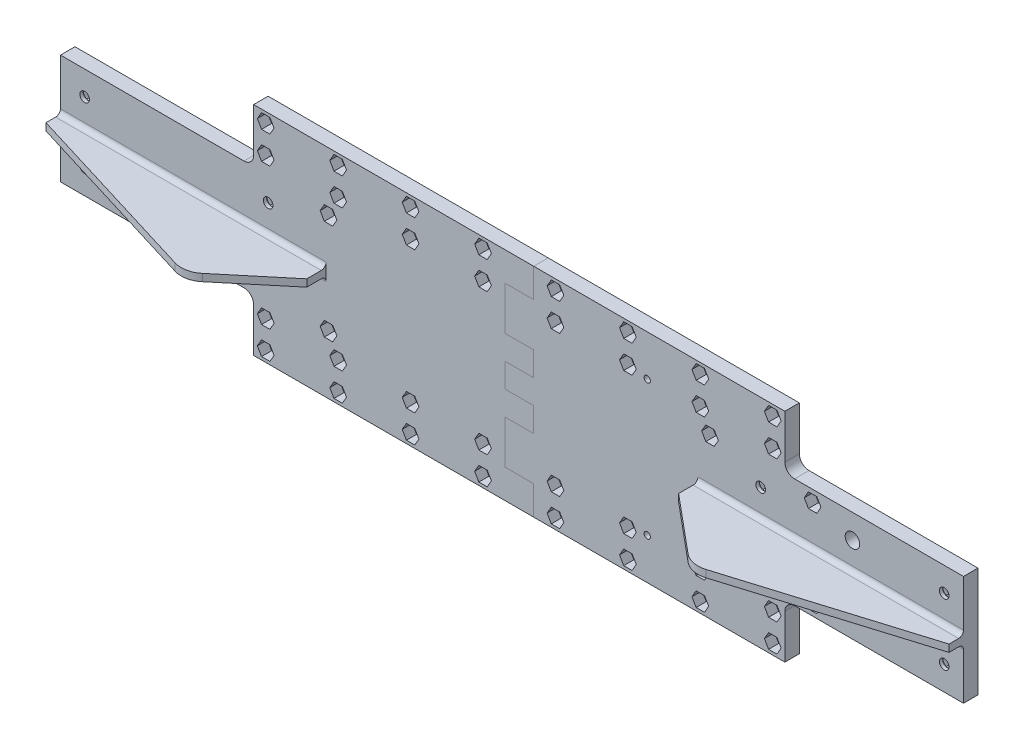
SolidWorks part; units mm, degrees
ref_plane "Top Plane" through (0, 0, 0) normal (0, 0, 1) x (1, 0, 0)
ref_plane "Right Plane" through (0, 0, 0) normal (0, 1, 0) x (1, 0, 0)
ref_plane "Front Plane" through (0, 0, 0) normal (1, 0, 0) x (0, 0, -1)
sketch "Sketch1" plane through (0, 0, 0) normal (0, 0, 1) x (1, 0, 0)
  line L0 (-187, 81) -> (187, -81) construction
  line L1 (-187, 81) -> (187, 81) construction
  line L2 (-187, 81) -> (-187, -81) construction
  line L3 (-187, -81) -> (187, -81) construction
  line L4 (187, 81) -> (187, -81) construction
  line L5 (-187, -22.75) -> (-107, -22.75) construction
  line L6 (-107, -22.75) -> (-107, -81) construction
  line L7 (113, -81) -> (113, -22.75) construction
  line L8 (113, -22.75) -> (187, -22.75) construction
  line L9 (-187, 0) -> (187, 0) construction
  line L10 (113, 22.75) -> (187, 22.75) construction
  line L11 (113, 81) -> (113, 22.75) construction
  line L12 (-107, 22.75) -> (-107, 81) construction
  line L13 (-187, 22.75) -> (-107, 22.75) construction
  line L14 (85.2, -81) -> (85.2, 81) construction
  line L15 (-93, -81) -> (-93, 81) construction
  line L16 (-187, -2.75) -> (187, -2.75) construction
  line L17 (187, 2.75) -> (-187, 2.75) construction
  text T0 "FRONT" font "Century Gothic" height in points 80
  dimension "D1" = 374
  dimension "D2" = 162
  dimension "D3" = 45.5
  dimension "D4" = 80
  dimension "D5" = 74
  dimension "D6" = 27.8
  dimension "D7" = 14
  dimension "D8" = 20
  dimension "D9" = 20
sketch "Sketch2" plane through (0, 0, 0) normal (0, 0, 1) x (1, 0, 0)
  line L0 (-187, 81) -> (-187, -81) construction
  line L1 (-187, 81) -> (187, 81) construction
  line L2 (187, 81) -> (187, -81) construction
  line L3 (-187, -81) -> (187, -81) construction
  line L4 (113, -81) -> (113, -22.75) construction
  line L5 (113, -22.75) -> (187, -22.75) construction
  line L6 (113, 22.75) -> (187, 22.75) construction
  line L7 (113, 81) -> (113, 22.75) construction
  line L8 (-107, 22.75) -> (-107, 81) construction
  line L9 (-187, 22.75) -> (-107, 22.75) construction
  line L10 (-107, -22.75) -> (-107, -81) construction
  line L11 (-187, -22.75) -> (-107, -22.75) construction
  line L12 (-187, 22.75) -> (-187, -22.75)
  line L13 (-107, 81) -> (113, 81)
  line L14 (187, 22.75) -> (187, -22.75)
  line L15 (-107, -81) -> (113, -81)
  line L16 (113, -81) -> (113, -22.75)
  line L17 (113, -22.75) -> (187, -22.75)
  line L18 (113, 22.75) -> (187, 22.75)
  line L19 (113, 81) -> (113, 22.75)
  line L20 (-107, 22.75) -> (-107, 81)
  line L21 (-187, 22.75) -> (-107, 22.75)
  line L22 (-107, -22.75) -> (-107, -81)
  line L23 (-187, -22.75) -> (-107, -22.75)
extrude "Boss-Extrude1" add sketch "Sketch2" along normal mid plane 6
sketch "Sketch5" plane through (0, 0, -3) normal (0, 0, -1) x (-1, 0, 0)
  line L0 (0, 81) -> (0, -81) construction
  line L1 (187, 81) -> (-187, 81) construction
  line L2 (187, -81) -> (-187, -81) construction
  line L4 (-179, 0) -> (177, 0) construction
  line L5 (-179, 12.75) -> (-103, 12.75) construction
  line L6 (-179, 12.75) -> (-179, -12.75) construction
  line L7 (-179, -12.75) -> (-103, -12.75) construction
  line L8 (-103, 12.75) -> (-103, -12.75) construction
  line L9 (101, 12.75) -> (177, 12.75) construction
  line L10 (101, 12.75) -> (101, -12.75) construction
  line L11 (101, -12.75) -> (177, -12.75) construction
  line L12 (177, 12.75) -> (177, -12.75) construction
  circle A8 centre (-103, -12.75) radius 2
  circle A9 centre (-103, 12.75) radius 2
  circle A10 centre (-179, 12.75) radius 2
  circle A11 centre (-179, -12.75) radius 2
  circle A12 centre (177, 12.75) radius 2
  circle A13 centre (177, -12.75) radius 2
  circle A14 centre (101, -12.75) radius 2
  circle A15 centre (101, 12.75) radius 2
  dimension "D3" = 25.5
  dimension "D6" = 4
  dimension "D1" = 76
  dimension "D2" = 103
  dimension "D4" = 101
  dimension "D5" = 76
extrude "Cut-Extrude2" cut sketch "Sketch5" against normal up to next
sketch "Sketch9" plane through (0, 0, 3) normal (0, 0, 1) x (1, 0, 0)
  line L0 (-107.9535, -35) -> (101.269, -35) construction
  line L1 (-12, -40.75) -> (18, -40.75) construction
  line L2 (-12, -29.25) -> (-42, -29.25) construction
  line L3 (-12, -29.25) -> (18, -29.25) construction
  line L4 (-194.5845, 0) -> (205.1662, 0) construction
  line L5 (3, -85.4344) -> (3, 85.4344) construction
  line L6 (-12, -40.75) -> (-42, -40.75) construction
  line L7 (-107, 81) -> (113, -81) construction
  line L8 (-40.2679, -37.75) -> (-43.7321, -37.75) construction
  line L9 (-13.7321, -37.75) -> (-15.4641, -40.75) construction
  line L10 (-15.4641, -40.75) -> (-13.7321, -43.75) construction
  line L11 (-13.7321, -43.75) -> (-10.2679, -43.75) construction
  line L12 (-10.2679, -43.75) -> (-8.5359, -40.75) construction
  line L13 (-8.5359, -40.75) -> (-10.2679, -37.75) construction
  line L14 (-10.2679, -37.75) -> (-13.7321, -37.75) construction
  line L15 (-43.7321, -37.75) -> (-45.4641, -40.75) construction
  line L16 (-45.4641, -40.75) -> (-43.7321, -43.75) construction
  line L17 (-43.7321, -43.75) -> (-40.2679, -43.75) construction
  line L18 (-40.2679, -43.75) -> (-38.5359, -40.75) construction
  line L19 (-38.5359, -40.75) -> (-40.2679, -37.75) construction
  line L20 (-70.2679, -37.75) -> (-73.7321, -37.75) construction
  line L21 (-73.7321, -37.75) -> (-75.4641, -40.75) construction
  line L22 (-75.4641, -40.75) -> (-73.7321, -43.75) construction
  line L23 (-73.7321, -43.75) -> (-70.2679, -43.75) construction
  line L24 (-70.2679, -43.75) -> (-68.5359, -40.75) construction
  line L25 (-68.5359, -40.75) -> (-70.2679, -37.75) construction
  line L26 (-100.2679, -37.75) -> (-103.7321, -37.75) construction
  line L27 (-103.7321, -37.75) -> (-105.4641, -40.75) construction
  line L28 (-105.4641, -40.75) -> (-103.7321, -43.75) construction
  line L29 (-103.7321, -43.75) -> (-100.2679, -43.75) construction
  line L30 (-100.2679, -43.75) -> (-98.5359, -40.75) construction
  line L31 (-98.5359, -40.75) -> (-100.2679, -37.75) construction
  line L32 (-43.7321, -37.75) -> (-40.2679, -43.75) construction
  line L33 (-42, -40.75) -> (-12, -40.75) construction
  line L34 (-8.5359, -29.25) -> (-10.2679, -32.25) construction
  line L35 (-10.2679, -26.25) -> (-8.5359, -29.25) construction
  line L36 (-13.7321, -26.25) -> (-10.2679, -26.25) construction
  line L37 (-15.4641, -29.25) -> (-13.7321, -26.25) construction
  line L38 (-13.7321, -32.25) -> (-15.4641, -29.25) construction
  line L39 (-10.2679, -32.25) -> (-13.7321, -32.25) construction
  line L40 (-43.7321, -26.25) -> (-40.2679, -26.25) construction
  line L41 (-45.4641, -29.25) -> (-43.7321, -26.25) construction
  line L42 (-43.7321, -32.25) -> (-45.4641, -29.25) construction
  line L43 (-40.2679, -32.25) -> (-43.7321, -32.25) construction
  line L44 (-38.5359, -29.25) -> (-40.2679, -32.25) construction
  line L45 (-40.2679, -26.25) -> (-38.5359, -29.25) construction
  line L46 (-73.7321, -26.25) -> (-70.2679, -26.25) construction
  line L47 (-75.4641, -29.25) -> (-73.7321, -26.25) construction
  line L48 (-73.7321, -32.25) -> (-75.4641, -29.25) construction
  line L49 (-70.2679, -32.25) -> (-73.7321, -32.25) construction
  line L50 (-68.5359, -29.25) -> (-70.2679, -32.25) construction
  line L51 (-70.2679, -26.25) -> (-68.5359, -29.25) construction
  line L52 (-103.7321, -26.25) -> (-100.2679, -26.25) construction
  line L53 (-105.4641, -29.25) -> (-103.7321, -26.25) construction
  line L54 (-103.7321, -32.25) -> (-105.4641, -29.25) construction
  line L55 (-100.2679, -32.25) -> (-103.7321, -32.25) construction
  line L56 (-98.5359, -29.25) -> (-100.2679, -32.25) construction
  line L57 (-100.2679, -26.25) -> (-98.5359, -29.25) construction
  line L58 (106.2679, -26.25) -> (104.5359, -29.25) construction
  line L59 (104.5359, -29.25) -> (106.2679, -32.25) construction
  line L60 (106.2679, -32.25) -> (109.7321, -32.25) construction
  line L61 (109.7321, -32.25) -> (111.4641, -29.25) construction
  line L62 (111.4641, -29.25) -> (109.7321, -26.25) construction
  line L63 (109.7321, -26.25) -> (106.2679, -26.25) construction
  line L64 (76.2679, -26.25) -> (74.5359, -29.25) construction
  line L65 (74.5359, -29.25) -> (76.2679, -32.25) construction
  line L66 (76.2679, -32.25) -> (79.7321, -32.25) construction
  line L67 (79.7321, -32.25) -> (81.4641, -29.25) construction
  line L68 (81.4641, -29.25) -> (79.7321, -26.25) construction
  line L69 (79.7321, -26.25) -> (76.2679, -26.25) construction
  line L70 (46.2679, -26.25) -> (44.5359, -29.25) construction
  line L71 (44.5359, -29.25) -> (46.2679, -32.25) construction
  line L72 (46.2679, -32.25) -> (49.7321, -32.25) construction
  line L73 (49.7321, -32.25) -> (51.4641, -29.25) construction
  line L74 (51.4641, -29.25) -> (49.7321, -26.25) construction
  line L75 (49.7321, -26.25) -> (46.2679, -26.25) construction
  line L76 (16.2679, -32.25) -> (19.7321, -32.25) construction
  line L77 (19.7321, -32.25) -> (21.4641, -29.25) construction
  line L78 (21.4641, -29.25) -> (19.7321, -26.25) construction
  line L79 (19.7321, -26.25) -> (16.2679, -26.25) construction
  line L80 (16.2679, -26.25) -> (14.5359, -29.25) construction
  line L81 (14.5359, -29.25) -> (16.2679, -32.25) construction
  line L82 (48, -40.75) -> (18, -40.75) construction
  line L83 (49.7321, -37.75) -> (46.2679, -43.75) construction
  line L84 (104.5359, -40.75) -> (106.2679, -37.75) construction
  line L85 (106.2679, -43.75) -> (104.5359, -40.75) construction
  line L86 (109.7321, -43.75) -> (106.2679, -43.75) construction
  line L87 (111.4641, -40.75) -> (109.7321, -43.75) construction
  line L88 (109.7321, -37.75) -> (111.4641, -40.75) construction
  line L89 (106.2679, -37.75) -> (109.7321, -37.75) construction
  line L90 (74.5359, -40.75) -> (76.2679, -37.75) construction
  line L91 (76.2679, -43.75) -> (74.5359, -40.75) construction
  line L92 (79.7321, -43.75) -> (76.2679, -43.75) construction
  line L93 (81.4641, -40.75) -> (79.7321, -43.75) construction
  line L94 (79.7321, -37.75) -> (81.4641, -40.75) construction
  line L95 (76.2679, -37.75) -> (79.7321, -37.75) construction
  line L96 (44.5359, -40.75) -> (46.2679, -37.75) construction
  line L97 (46.2679, -43.75) -> (44.5359, -40.75) construction
  line L98 (49.7321, -43.75) -> (46.2679, -43.75) construction
  line L99 (51.4641, -40.75) -> (49.7321, -43.75) construction
  line L100 (49.7321, -37.75) -> (51.4641, -40.75) construction
  line L101 (16.2679, -37.75) -> (19.7321, -37.75) construction
  line L102 (14.5359, -40.75) -> (16.2679, -37.75) construction
  line L103 (16.2679, -43.75) -> (14.5359, -40.75) construction
  line L104 (19.7321, -43.75) -> (16.2679, -43.75) construction
  line L105 (21.4641, -40.75) -> (19.7321, -43.75) construction
  line L106 (19.7321, -37.75) -> (21.4641, -40.75) construction
  line L107 (46.2679, -37.75) -> (49.7321, -37.75) construction
  line L108 (46.2679, 37.75) -> (49.7321, 37.75) construction
  line L109 (19.7321, 37.75) -> (21.4641, 40.75) construction
  line L110 (21.4641, 40.75) -> (19.7321, 43.75) construction
  line L111 (19.7321, 43.75) -> (16.2679, 43.75) construction
  line L112 (16.2679, 43.75) -> (14.5359, 40.75) construction
  line L113 (14.5359, 40.75) -> (16.2679, 37.75) construction
  line L114 (16.2679, 37.75) -> (19.7321, 37.75) construction
  line L115 (49.7321, 37.75) -> (51.4641, 40.75) construction
  line L116 (51.4641, 40.75) -> (49.7321, 43.75) construction
  line L117 (49.7321, 43.75) -> (46.2679, 43.75) construction
  line L118 (46.2679, 43.75) -> (44.5359, 40.75) construction
  line L119 (44.5359, 40.75) -> (46.2679, 37.75) construction
  line L120 (76.2679, 37.75) -> (79.7321, 37.75) construction
  line L121 (79.7321, 37.75) -> (81.4641, 40.75) construction
  line L122 (81.4641, 40.75) -> (79.7321, 43.75) construction
  line L123 (79.7321, 43.75) -> (76.2679, 43.75) construction
  line L124 (76.2679, 43.75) -> (74.5359, 40.75) construction
  line L125 (74.5359, 40.75) -> (76.2679, 37.75) construction
  line L126 (106.2679, 37.75) -> (109.7321, 37.75) construction
  line L127 (109.7321, 37.75) -> (111.4641, 40.75) construction
  line L128 (111.4641, 40.75) -> (109.7321, 43.75) construction
  line L129 (109.7321, 43.75) -> (106.2679, 43.75) construction
  line L130 (106.2679, 43.75) -> (104.5359, 40.75) construction
  line L131 (104.5359, 40.75) -> (106.2679, 37.75) construction
  line L132 (49.7321, 37.75) -> (46.2679, 43.75) construction
  line L133 (48, 40.75) -> (18, 40.75) construction
  line L134 (14.5359, 29.25) -> (16.2679, 32.25) construction
  line L135 (16.2679, 26.25) -> (14.5359, 29.25) construction
  line L136 (19.7321, 26.25) -> (16.2679, 26.25) construction
  line L137 (21.4641, 29.25) -> (19.7321, 26.25) construction
  line L138 (19.7321, 32.25) -> (21.4641, 29.25) construction
  line L139 (16.2679, 32.25) -> (19.7321, 32.25) construction
  line L140 (49.7321, 26.25) -> (46.2679, 26.25) construction
  line L141 (51.4641, 29.25) -> (49.7321, 26.25) construction
  line L142 (49.7321, 32.25) -> (51.4641, 29.25) construction
  line L143 (46.2679, 32.25) -> (49.7321, 32.25) construction
  line L144 (44.5359, 29.25) -> (46.2679, 32.25) construction
  line L145 (46.2679, 26.25) -> (44.5359, 29.25) construction
  line L146 (79.7321, 26.25) -> (76.2679, 26.25) construction
  line L147 (81.4641, 29.25) -> (79.7321, 26.25) construction
  line L148 (79.7321, 32.25) -> (81.4641, 29.25) construction
  line L149 (76.2679, 32.25) -> (79.7321, 32.25) construction
  line L150 (74.5359, 29.25) -> (76.2679, 32.25) construction
  line L151 (76.2679, 26.25) -> (74.5359, 29.25) construction
  line L152 (109.7321, 26.25) -> (106.2679, 26.25) construction
  line L153 (111.4641, 29.25) -> (109.7321, 26.25) construction
  line L154 (109.7321, 32.25) -> (111.4641, 29.25) construction
  line L155 (106.2679, 32.25) -> (109.7321, 32.25) construction
  line L156 (104.5359, 29.25) -> (106.2679, 32.25) construction
  line L157 (106.2679, 26.25) -> (104.5359, 29.25) construction
  line L158 (-100.2679, 26.25) -> (-98.5359, 29.25) construction
  line L159 (-98.5359, 29.25) -> (-100.2679, 32.25) construction
  line L160 (-100.2679, 32.25) -> (-103.7321, 32.25) construction
  line L161 (-103.7321, 32.25) -> (-105.4641, 29.25) construction
  line L162 (-105.4641, 29.25) -> (-103.7321, 26.25) construction
  line L163 (-103.7321, 26.25) -> (-100.2679, 26.25) construction
  line L164 (-70.2679, 26.25) -> (-68.5359, 29.25) construction
  line L165 (-68.5359, 29.25) -> (-70.2679, 32.25) construction
  line L166 (-70.2679, 32.25) -> (-73.7321, 32.25) construction
  line L167 (-73.7321, 32.25) -> (-75.4641, 29.25) construction
  line L168 (-75.4641, 29.25) -> (-73.7321, 26.25) construction
  line L169 (-73.7321, 26.25) -> (-70.2679, 26.25) construction
  line L170 (-40.2679, 26.25) -> (-38.5359, 29.25) construction
  line L171 (-38.5359, 29.25) -> (-40.2679, 32.25) construction
  line L172 (-40.2679, 32.25) -> (-43.7321, 32.25) construction
  line L173 (-43.7321, 32.25) -> (-45.4641, 29.25) construction
  line L174 (-45.4641, 29.25) -> (-43.7321, 26.25) construction
  line L175 (-43.7321, 26.25) -> (-40.2679, 26.25) construction
  line L176 (-10.2679, 32.25) -> (-13.7321, 32.25) construction
  line L177 (-13.7321, 32.25) -> (-15.4641, 29.25) construction
  line L178 (-15.4641, 29.25) -> (-13.7321, 26.25) construction
  line L179 (-13.7321, 26.25) -> (-10.2679, 26.25) construction
  line L180 (-10.2679, 26.25) -> (-8.5359, 29.25) construction
  line L181 (-8.5359, 29.25) -> (-10.2679, 32.25) construction
  line L182 (-42, 40.75) -> (-12, 40.75) construction
  line L183 (-43.7321, 37.75) -> (-40.2679, 43.75) construction
  line L184 (-98.5359, 40.75) -> (-100.2679, 37.75) construction
  line L185 (-100.2679, 43.75) -> (-98.5359, 40.75) construction
  line L186 (-103.7321, 43.75) -> (-100.2679, 43.75) construction
  line L187 (-105.4641, 40.75) -> (-103.7321, 43.75) construction
  line L188 (-103.7321, 37.75) -> (-105.4641, 40.75) construction
  line L189 (-100.2679, 37.75) -> (-103.7321, 37.75) construction
  line L190 (-68.5359, 40.75) -> (-70.2679, 37.75) construction
  line L191 (-70.2679, 43.75) -> (-68.5359, 40.75) construction
  line L192 (-73.7321, 43.75) -> (-70.2679, 43.75) construction
  line L193 (-75.4641, 40.75) -> (-73.7321, 43.75) construction
  line L194 (-73.7321, 37.75) -> (-75.4641, 40.75) construction
  line L195 (-70.2679, 37.75) -> (-73.7321, 37.75) construction
  line L196 (-38.5359, 40.75) -> (-40.2679, 37.75) construction
  line L197 (-40.2679, 43.75) -> (-38.5359, 40.75) construction
  line L198 (-43.7321, 43.75) -> (-40.2679, 43.75) construction
  line L199 (-45.4641, 40.75) -> (-43.7321, 43.75) construction
  line L200 (-43.7321, 37.75) -> (-45.4641, 40.75) construction
  line L201 (-10.2679, 37.75) -> (-13.7321, 37.75) construction
  line L202 (-8.5359, 40.75) -> (-10.2679, 37.75) construction
  line L203 (-10.2679, 43.75) -> (-8.5359, 40.75) construction
  line L204 (-13.7321, 43.75) -> (-10.2679, 43.75) construction
  line L205 (-15.4641, 40.75) -> (-13.7321, 43.75) construction
  line L206 (-13.7321, 37.75) -> (-15.4641, 40.75) construction
  line L207 (-40.2679, 37.75) -> (-43.7321, 37.75) construction
  line L208 (-12, 40.75) -> (-42, 40.75) construction
  line L209 (-12, 29.25) -> (18, 29.25) construction
  line L210 (-12, 29.25) -> (-42, 29.25) construction
  line L211 (-12, 40.75) -> (18, 40.75) construction
  line L212 (-107.9535, 35) -> (101.269, 35) construction
  circle A0 centre (-12, -40.75) radius 1.75
  circle A1 centre (-42, -40.75) radius 1.75
  circle A2 centre (-72, -40.75) radius 1.75
  circle A3 centre (-102, -40.75) radius 1.75
  circle A4 centre (108, -40.75) radius 1.75
  circle A5 centre (78, -40.75) radius 1.75
  circle A6 centre (48, -40.75) radius 1.75
  circle A7 centre (18, -40.75) radius 1.75
  circle A8 centre (18, -29.25) radius 1.75
  circle A9 centre (48, -29.25) radius 1.75
  circle A10 centre (78, -29.25) radius 1.75
  circle A11 centre (108, -29.25) radius 1.75
  circle A12 centre (-102, -29.25) radius 1.75
  circle A13 centre (-72, -29.25) radius 1.75
  circle A14 centre (-42, -29.25) radius 1.75
  circle A15 centre (-12, -29.25) radius 1.75
  circle A16 centre (-12, -40.75) radius 3 construction
  circle A17 centre (-12, 40.75) radius 3 construction
  circle A18 centre (-12, 29.25) radius 1.75
  circle A19 centre (-42, 29.25) radius 1.75
  circle A20 centre (-72, 29.25) radius 1.75
  circle A21 centre (-102, 29.25) radius 1.75
  circle A22 centre (108, 29.25) radius 1.75
  circle A23 centre (78, 29.25) radius 1.75
  circle A24 centre (48, 29.25) radius 1.75
  circle A25 centre (18, 29.25) radius 1.75
  circle A26 centre (18, 40.75) radius 1.75
  circle A27 centre (48, 40.75) radius 1.75
  circle A28 centre (78, 40.75) radius 1.75
  circle A29 centre (108, 40.75) radius 1.75
  circle A30 centre (-102, 40.75) radius 1.75
  circle A31 centre (-72, 40.75) radius 1.75
  circle A32 centre (-42, 40.75) radius 1.75
  circle A33 centre (-12, 40.75) radius 1.75
  point P6 (3, -40.75)
  point P39 (3, -29.25)
  point P46 (3, 0)
  point P277 (3, 29.25)
  point P278 (3, 40.75)
  dimension "D3" = 3.5
  dimension "D1" = 11.5
  dimension "D2" = 35
  dimension "D5" = 30
  dimension "D6" = 6
  dimension "D4" = 4
  dimension "D7" = 4
extrude "Cut-Extrude6" cut sketch "Sketch9" against normal through all
sketch "Sketch10" plane through (0, 0, 3) normal (0, 0, 1) x (1, 0, 0)
  line L0 (-103.7321, -43.75) -> (-100.2679, -43.75) construction
  line L1 (-105.4641, -40.75) -> (-103.7321, -43.75) construction
  line L2 (-103.7321, -37.75) -> (-105.4641, -40.75) construction
  line L3 (-100.2679, -37.75) -> (-103.7321, -37.75) construction
  line L4 (-98.5359, -40.75) -> (-100.2679, -37.75) construction
  line L5 (-100.2679, -43.75) -> (-98.5359, -40.75) construction
  line L6 (-103.7321, -43.75) -> (-100.2679, -43.75)
  line L7 (-105.4641, -40.75) -> (-103.7321, -43.75)
  line L8 (-103.7321, -37.75) -> (-105.4641, -40.75)
  line L9 (-100.2679, -37.75) -> (-103.7321, -37.75)
  line L10 (-98.5359, -40.75) -> (-100.2679, -37.75)
  line L11 (-100.2679, -43.75) -> (-98.5359, -40.75)
  line L12 (-73.7321, -43.75) -> (-70.2679, -43.75) construction
  line L13 (-75.4641, -40.75) -> (-73.7321, -43.75) construction
  line L14 (-73.7321, -37.75) -> (-75.4641, -40.75) construction
  line L15 (-70.2679, -37.75) -> (-73.7321, -37.75) construction
  line L16 (-68.5359, -40.75) -> (-70.2679, -37.75) construction
  line L17 (-70.2679, -43.75) -> (-68.5359, -40.75) construction
  line L18 (-73.7321, -43.75) -> (-70.2679, -43.75)
  line L19 (-75.4641, -40.75) -> (-73.7321, -43.75)
  line L20 (-73.7321, -37.75) -> (-75.4641, -40.75)
  line L21 (-70.2679, -37.75) -> (-73.7321, -37.75)
  line L22 (-68.5359, -40.75) -> (-70.2679, -37.75)
  line L23 (-70.2679, -43.75) -> (-68.5359, -40.75)
  line L24 (-43.7321, -43.75) -> (-40.2679, -43.75) construction
  line L25 (-45.4641, -40.75) -> (-43.7321, -43.75) construction
  line L26 (-43.7321, -37.75) -> (-45.4641, -40.75) construction
  line L27 (-40.2679, -37.75) -> (-43.7321, -37.75) construction
  line L28 (-38.5359, -40.75) -> (-40.2679, -37.75) construction
  line L29 (-40.2679, -43.75) -> (-38.5359, -40.75) construction
  line L30 (-43.7321, -43.75) -> (-40.2679, -43.75)
  line L31 (-45.4641, -40.75) -> (-43.7321, -43.75)
  line L32 (-43.7321, -37.75) -> (-45.4641, -40.75)
  line L33 (-40.2679, -37.75) -> (-43.7321, -37.75)
  line L34 (-38.5359, -40.75) -> (-40.2679, -37.75)
  line L35 (-40.2679, -43.75) -> (-38.5359, -40.75)
  line L36 (-13.7321, -43.75) -> (-10.2679, -43.75) construction
  line L37 (-15.4641, -40.75) -> (-13.7321, -43.75) construction
  line L38 (-13.7321, -37.75) -> (-15.4641, -40.75) construction
  line L39 (-10.2679, -37.75) -> (-13.7321, -37.75) construction
  line L40 (-8.5359, -40.75) -> (-10.2679, -37.75) construction
  line L41 (-10.2679, -43.75) -> (-8.5359, -40.75) construction
  line L42 (-13.7321, -43.75) -> (-10.2679, -43.75)
  line L43 (-15.4641, -40.75) -> (-13.7321, -43.75)
  line L44 (-13.7321, -37.75) -> (-15.4641, -40.75)
  line L45 (-10.2679, -37.75) -> (-13.7321, -37.75)
  line L46 (-8.5359, -40.75) -> (-10.2679, -37.75)
  line L47 (-10.2679, -43.75) -> (-8.5359, -40.75)
  line L48 (79.7321, -43.75) -> (76.2679, -43.75) construction
  line L49 (81.4641, -40.75) -> (79.7321, -43.75) construction
  line L50 (79.7321, -37.75) -> (81.4641, -40.75) construction
  line L51 (76.2679, -37.75) -> (79.7321, -37.75) construction
  line L52 (74.5359, -40.75) -> (76.2679, -37.75) construction
  line L53 (76.2679, -43.75) -> (74.5359, -40.75) construction
  line L54 (46.2679, -37.75) -> (49.7321, -37.75) construction
  line L55 (44.5359, -40.75) -> (46.2679, -37.75) construction
  line L56 (46.2679, -43.75) -> (44.5359, -40.75) construction
  line L57 (16.2679, -43.75) -> (14.5359, -40.75) construction
  line L58 (19.7321, -43.75) -> (16.2679, -43.75) construction
  line L59 (21.4641, -40.75) -> (19.7321, -43.75) construction
  line L60 (19.7321, -37.75) -> (21.4641, -40.75) construction
  line L61 (16.2679, -37.75) -> (19.7321, -37.75) construction
  line L62 (14.5359, -40.75) -> (16.2679, -37.75) construction
  line L63 (79.7321, -43.75) -> (76.2679, -43.75)
  line L64 (81.4641, -40.75) -> (79.7321, -43.75)
  line L65 (79.7321, -37.75) -> (81.4641, -40.75)
  line L66 (76.2679, -37.75) -> (79.7321, -37.75)
  line L67 (74.5359, -40.75) -> (76.2679, -37.75)
  line L68 (76.2679, -43.75) -> (74.5359, -40.75)
  line L69 (46.2679, -37.75) -> (49.7321, -37.75)
  line L70 (44.5359, -40.75) -> (46.2679, -37.75)
  line L71 (46.2679, -43.75) -> (44.5359, -40.75)
  line L72 (16.2679, -43.75) -> (14.5359, -40.75)
  line L73 (19.7321, -43.75) -> (16.2679, -43.75)
  line L74 (21.4641, -40.75) -> (19.7321, -43.75)
  line L75 (19.7321, -37.75) -> (21.4641, -40.75)
  line L76 (16.2679, -37.75) -> (19.7321, -37.75)
  line L77 (14.5359, -40.75) -> (16.2679, -37.75)
  line L78 (49.7321, -43.75) -> (46.2679, -43.75) construction
  line L79 (51.4641, -40.75) -> (49.7321, -43.75) construction
  line L80 (49.7321, -37.75) -> (51.4641, -40.75) construction
  line L81 (49.7321, -43.75) -> (46.2679, -43.75)
  line L82 (51.4641, -40.75) -> (49.7321, -43.75)
  line L83 (49.7321, -37.75) -> (51.4641, -40.75)
  line L84 (46.2679, -32.25) -> (49.7321, -32.25) construction
  line L85 (44.5359, -29.25) -> (46.2679, -32.25) construction
  line L86 (46.2679, -26.25) -> (44.5359, -29.25) construction
  line L87 (49.7321, -26.25) -> (46.2679, -26.25) construction
  line L88 (51.4641, -29.25) -> (49.7321, -26.25) construction
  line L89 (49.7321, -32.25) -> (51.4641, -29.25) construction
  line L90 (79.7321, -32.25) -> (81.4641, -29.25) construction
  line L91 (76.2679, -32.25) -> (79.7321, -32.25) construction
  line L92 (74.5359, -29.25) -> (76.2679, -32.25) construction
  line L93 (76.2679, -26.25) -> (74.5359, -29.25) construction
  line L94 (79.7321, -26.25) -> (76.2679, -26.25) construction
  line L95 (81.4641, -29.25) -> (79.7321, -26.25) construction
  line L96 (106.2679, -26.25) -> (104.5359, -29.25) construction
  line L97 (109.7321, -26.25) -> (106.2679, -26.25) construction
  line L98 (111.4641, -29.25) -> (109.7321, -26.25) construction
  line L99 (109.7321, -32.25) -> (111.4641, -29.25) construction
  line L100 (106.2679, -32.25) -> (109.7321, -32.25) construction
  line L101 (104.5359, -29.25) -> (106.2679, -32.25) construction
  line L102 (106.2679, -43.75) -> (104.5359, -40.75) construction
  line L103 (109.7321, -43.75) -> (106.2679, -43.75) construction
  line L104 (111.4641, -40.75) -> (109.7321, -43.75) construction
  line L105 (109.7321, -37.75) -> (111.4641, -40.75) construction
  line L106 (106.2679, -37.75) -> (109.7321, -37.75) construction
  line L107 (104.5359, -40.75) -> (106.2679, -37.75) construction
  line L108 (46.2679, -32.25) -> (49.7321, -32.25)
  line L109 (44.5359, -29.25) -> (46.2679, -32.25)
  line L110 (46.2679, -26.25) -> (44.5359, -29.25)
  line L111 (49.7321, -26.25) -> (46.2679, -26.25)
  line L112 (51.4641, -29.25) -> (49.7321, -26.25)
  line L113 (49.7321, -32.25) -> (51.4641, -29.25)
  line L114 (79.7321, -32.25) -> (81.4641, -29.25)
  line L115 (76.2679, -32.25) -> (79.7321, -32.25)
  line L116 (74.5359, -29.25) -> (76.2679, -32.25)
  line L117 (76.2679, -26.25) -> (74.5359, -29.25)
  line L118 (79.7321, -26.25) -> (76.2679, -26.25)
  line L119 (81.4641, -29.25) -> (79.7321, -26.25)
  line L120 (106.2679, -26.25) -> (104.5359, -29.25)
  line L121 (109.7321, -26.25) -> (106.2679, -26.25)
  line L122 (111.4641, -29.25) -> (109.7321, -26.25)
  line L123 (109.7321, -32.25) -> (111.4641, -29.25)
  line L124 (106.2679, -32.25) -> (109.7321, -32.25)
  line L125 (104.5359, -29.25) -> (106.2679, -32.25)
  line L126 (106.2679, -43.75) -> (104.5359, -40.75)
  line L127 (109.7321, -43.75) -> (106.2679, -43.75)
  line L128 (111.4641, -40.75) -> (109.7321, -43.75)
  line L129 (109.7321, -37.75) -> (111.4641, -40.75)
  line L130 (106.2679, -37.75) -> (109.7321, -37.75)
  line L131 (104.5359, -40.75) -> (106.2679, -37.75)
  line L132 (-43.7321, -32.25) -> (-45.4641, -29.25) construction
  line L133 (-40.2679, -32.25) -> (-43.7321, -32.25) construction
  line L134 (-38.5359, -29.25) -> (-40.2679, -32.25) construction
  line L135 (-40.2679, -26.25) -> (-38.5359, -29.25) construction
  line L136 (-43.7321, -26.25) -> (-40.2679, -26.25) construction
  line L137 (-45.4641, -29.25) -> (-43.7321, -26.25) construction
  line L138 (-13.7321, -32.25) -> (-15.4641, -29.25) construction
  line L139 (-10.2679, -32.25) -> (-13.7321, -32.25) construction
  line L140 (-8.5359, -29.25) -> (-10.2679, -32.25) construction
  line L141 (-10.2679, -26.25) -> (-8.5359, -29.25) construction
  line L142 (-13.7321, -26.25) -> (-10.2679, -26.25) construction
  line L143 (-15.4641, -29.25) -> (-13.7321, -26.25) construction
  line L144 (19.7321, -32.25) -> (21.4641, -29.25) construction
  line L145 (16.2679, -32.25) -> (19.7321, -32.25) construction
  line L146 (14.5359, -29.25) -> (16.2679, -32.25) construction
  line L147 (16.2679, -26.25) -> (14.5359, -29.25) construction
  line L148 (19.7321, -26.25) -> (16.2679, -26.25) construction
  line L149 (21.4641, -29.25) -> (19.7321, -26.25) construction
  line L150 (-43.7321, -32.25) -> (-45.4641, -29.25)
  line L151 (-40.2679, -32.25) -> (-43.7321, -32.25)
  line L152 (-38.5359, -29.25) -> (-40.2679, -32.25)
  line L153 (-40.2679, -26.25) -> (-38.5359, -29.25)
  line L154 (-43.7321, -26.25) -> (-40.2679, -26.25)
  line L155 (-45.4641, -29.25) -> (-43.7321, -26.25)
  line L156 (-13.7321, -32.25) -> (-15.4641, -29.25)
  line L157 (-10.2679, -32.25) -> (-13.7321, -32.25)
  line L158 (-8.5359, -29.25) -> (-10.2679, -32.25)
  line L159 (-10.2679, -26.25) -> (-8.5359, -29.25)
  line L160 (-13.7321, -26.25) -> (-10.2679, -26.25)
  line L161 (-15.4641, -29.25) -> (-13.7321, -26.25)
  line L162 (19.7321, -32.25) -> (21.4641, -29.25)
  line L163 (16.2679, -32.25) -> (19.7321, -32.25)
  line L164 (14.5359, -29.25) -> (16.2679, -32.25)
  line L165 (16.2679, -26.25) -> (14.5359, -29.25)
  line L166 (19.7321, -26.25) -> (16.2679, -26.25)
  line L167 (21.4641, -29.25) -> (19.7321, -26.25)
  line L168 (-100.2679, -32.25) -> (-103.7321, -32.25) construction
  line L169 (-98.5359, -29.25) -> (-100.2679, -32.25) construction
  line L170 (-100.2679, -26.25) -> (-98.5359, -29.25) construction
  line L171 (-103.7321, -26.25) -> (-100.2679, -26.25) construction
  line L172 (-105.4641, -29.25) -> (-103.7321, -26.25) construction
  line L173 (-103.7321, -32.25) -> (-105.4641, -29.25) construction
  line L174 (-68.5359, -29.25) -> (-70.2679, -32.25) construction
  line L175 (-70.2679, -26.25) -> (-68.5359, -29.25) construction
  line L176 (-73.7321, -26.25) -> (-70.2679, -26.25) construction
  line L177 (-75.4641, -29.25) -> (-73.7321, -26.25) construction
  line L178 (-73.7321, -32.25) -> (-75.4641, -29.25) construction
  line L179 (-70.2679, -32.25) -> (-73.7321, -32.25) construction
  line L180 (-100.2679, -32.25) -> (-103.7321, -32.25)
  line L181 (-98.5359, -29.25) -> (-100.2679, -32.25)
  line L182 (-100.2679, -26.25) -> (-98.5359, -29.25)
  line L183 (-103.7321, -26.25) -> (-100.2679, -26.25)
  line L184 (-105.4641, -29.25) -> (-103.7321, -26.25)
  line L185 (-103.7321, -32.25) -> (-105.4641, -29.25)
  line L186 (-68.5359, -29.25) -> (-70.2679, -32.25)
  line L187 (-70.2679, -26.25) -> (-68.5359, -29.25)
  line L188 (-73.7321, -26.25) -> (-70.2679, -26.25)
  line L189 (-75.4641, -29.25) -> (-73.7321, -26.25)
  line L190 (-73.7321, -32.25) -> (-75.4641, -29.25)
  line L191 (-70.2679, -32.25) -> (-73.7321, -32.25)
  line L192 (-73.7321, 26.25) -> (-70.2679, 26.25) construction
  line L193 (-75.4641, 29.25) -> (-73.7321, 26.25) construction
  line L194 (-73.7321, 32.25) -> (-75.4641, 29.25) construction
  line L195 (-70.2679, 32.25) -> (-73.7321, 32.25) construction
  line L196 (-68.5359, 29.25) -> (-70.2679, 32.25) construction
  line L197 (-70.2679, 26.25) -> (-68.5359, 29.25) construction
  line L198 (-73.7321, 37.75) -> (-75.4641, 40.75) construction
  line L199 (-70.2679, 37.75) -> (-73.7321, 37.75) construction
  line L200 (-68.5359, 40.75) -> (-70.2679, 37.75) construction
  line L201 (-70.2679, 43.75) -> (-68.5359, 40.75) construction
  line L202 (-73.7321, 43.75) -> (-70.2679, 43.75) construction
  line L203 (-75.4641, 40.75) -> (-73.7321, 43.75) construction
  line L204 (-103.7321, 26.25) -> (-100.2679, 26.25) construction
  line L205 (-105.4641, 29.25) -> (-103.7321, 26.25) construction
  line L206 (-103.7321, 32.25) -> (-105.4641, 29.25) construction
  line L207 (-100.2679, 32.25) -> (-103.7321, 32.25) construction
  line L208 (-98.5359, 29.25) -> (-100.2679, 32.25) construction
  line L209 (-100.2679, 26.25) -> (-98.5359, 29.25) construction
  line L210 (-103.7321, 37.75) -> (-105.4641, 40.75) construction
  line L211 (-100.2679, 37.75) -> (-103.7321, 37.75) construction
  line L212 (-98.5359, 40.75) -> (-100.2679, 37.75) construction
  line L213 (-100.2679, 43.75) -> (-98.5359, 40.75) construction
  line L214 (-103.7321, 43.75) -> (-100.2679, 43.75) construction
  line L215 (-105.4641, 40.75) -> (-103.7321, 43.75) construction
  line L216 (-73.7321, 26.25) -> (-70.2679, 26.25)
  line L217 (-75.4641, 29.25) -> (-73.7321, 26.25)
  line L218 (-73.7321, 32.25) -> (-75.4641, 29.25)
  line L219 (-70.2679, 32.25) -> (-73.7321, 32.25)
  line L220 (-68.5359, 29.25) -> (-70.2679, 32.25)
  line L221 (-70.2679, 26.25) -> (-68.5359, 29.25)
  line L222 (-73.7321, 37.75) -> (-75.4641, 40.75)
  line L223 (-70.2679, 37.75) -> (-73.7321, 37.75)
  line L224 (-68.5359, 40.75) -> (-70.2679, 37.75)
  line L225 (-70.2679, 43.75) -> (-68.5359, 40.75)
  line L226 (-73.7321, 43.75) -> (-70.2679, 43.75)
  line L227 (-75.4641, 40.75) -> (-73.7321, 43.75)
  line L228 (-103.7321, 26.25) -> (-100.2679, 26.25)
  line L229 (-105.4641, 29.25) -> (-103.7321, 26.25)
  line L230 (-103.7321, 32.25) -> (-105.4641, 29.25)
  line L231 (-100.2679, 32.25) -> (-103.7321, 32.25)
  line L232 (-98.5359, 29.25) -> (-100.2679, 32.25)
  line L233 (-100.2679, 26.25) -> (-98.5359, 29.25)
  line L234 (-103.7321, 37.75) -> (-105.4641, 40.75)
  line L235 (-100.2679, 37.75) -> (-103.7321, 37.75)
  line L236 (-98.5359, 40.75) -> (-100.2679, 37.75)
  line L237 (-100.2679, 43.75) -> (-98.5359, 40.75)
  line L238 (-103.7321, 43.75) -> (-100.2679, 43.75)
  line L239 (-105.4641, 40.75) -> (-103.7321, 43.75)
  line L240 (-15.4641, 29.25) -> (-13.7321, 26.25) construction
  line L241 (-13.7321, 32.25) -> (-15.4641, 29.25) construction
  line L242 (-10.2679, 32.25) -> (-13.7321, 32.25) construction
  line L243 (-8.5359, 29.25) -> (-10.2679, 32.25) construction
  line L244 (-10.2679, 26.25) -> (-8.5359, 29.25) construction
  line L245 (-13.7321, 26.25) -> (-10.2679, 26.25) construction
  line L246 (-13.7321, 37.75) -> (-15.4641, 40.75) construction
  line L247 (-10.2679, 37.75) -> (-13.7321, 37.75) construction
  line L248 (-8.5359, 40.75) -> (-10.2679, 37.75) construction
  line L249 (-10.2679, 43.75) -> (-8.5359, 40.75) construction
  line L250 (-13.7321, 43.75) -> (-10.2679, 43.75) construction
  line L251 (-15.4641, 40.75) -> (-13.7321, 43.75) construction
  line L252 (-43.7321, 26.25) -> (-40.2679, 26.25) construction
  line L253 (-45.4641, 29.25) -> (-43.7321, 26.25) construction
  line L254 (-43.7321, 32.25) -> (-45.4641, 29.25) construction
  line L255 (-40.2679, 32.25) -> (-43.7321, 32.25) construction
  line L256 (-38.5359, 29.25) -> (-40.2679, 32.25) construction
  line L257 (-40.2679, 26.25) -> (-38.5359, 29.25) construction
  line L258 (-40.2679, 37.75) -> (-43.7321, 37.75) construction
  line L259 (-38.5359, 40.75) -> (-40.2679, 37.75) construction
  line L260 (-40.2679, 43.75) -> (-38.5359, 40.75) construction
  line L261 (-43.7321, 43.75) -> (-40.2679, 43.75) construction
  line L262 (-45.4641, 40.75) -> (-43.7321, 43.75) construction
  line L263 (-43.7321, 37.75) -> (-45.4641, 40.75) construction
  line L264 (-15.4641, 29.25) -> (-13.7321, 26.25)
  line L265 (-13.7321, 32.25) -> (-15.4641, 29.25)
  line L266 (-10.2679, 32.25) -> (-13.7321, 32.25)
  line L267 (-8.5359, 29.25) -> (-10.2679, 32.25)
  line L268 (-10.2679, 26.25) -> (-8.5359, 29.25)
  line L269 (-13.7321, 26.25) -> (-10.2679, 26.25)
  line L270 (-13.7321, 37.75) -> (-15.4641, 40.75)
  line L271 (-10.2679, 37.75) -> (-13.7321, 37.75)
  line L272 (-8.5359, 40.75) -> (-10.2679, 37.75)
  line L273 (-10.2679, 43.75) -> (-8.5359, 40.75)
  line L274 (-13.7321, 43.75) -> (-10.2679, 43.75)
  line L275 (-15.4641, 40.75) -> (-13.7321, 43.75)
  line L276 (-43.7321, 26.25) -> (-40.2679, 26.25)
  line L277 (-45.4641, 29.25) -> (-43.7321, 26.25)
  line L278 (-43.7321, 32.25) -> (-45.4641, 29.25)
  line L279 (-40.2679, 32.25) -> (-43.7321, 32.25)
  line L280 (-38.5359, 29.25) -> (-40.2679, 32.25)
  line L281 (-40.2679, 26.25) -> (-38.5359, 29.25)
  line L282 (-40.2679, 37.75) -> (-43.7321, 37.75)
  line L283 (-38.5359, 40.75) -> (-40.2679, 37.75)
  line L284 (-40.2679, 43.75) -> (-38.5359, 40.75)
  line L285 (-43.7321, 43.75) -> (-40.2679, 43.75)
  line L286 (-45.4641, 40.75) -> (-43.7321, 43.75)
  line L287 (-43.7321, 37.75) -> (-45.4641, 40.75)
  line L288 (46.2679, 26.25) -> (44.5359, 29.25) construction
  line L289 (49.7321, 26.25) -> (46.2679, 26.25) construction
  line L290 (51.4641, 29.25) -> (49.7321, 26.25) construction
  line L291 (49.7321, 32.25) -> (51.4641, 29.25) construction
  line L292 (46.2679, 32.25) -> (49.7321, 32.25) construction
  line L293 (44.5359, 29.25) -> (46.2679, 32.25) construction
  line L294 (46.2679, 37.75) -> (49.7321, 37.75) construction
  line L295 (44.5359, 40.75) -> (46.2679, 37.75) construction
  line L296 (46.2679, 43.75) -> (44.5359, 40.75) construction
  line L297 (49.7321, 43.75) -> (46.2679, 43.75) construction
  line L298 (51.4641, 40.75) -> (49.7321, 43.75) construction
  line L299 (49.7321, 37.75) -> (51.4641, 40.75) construction
  line L300 (16.2679, 26.25) -> (14.5359, 29.25) construction
  line L301 (19.7321, 26.25) -> (16.2679, 26.25) construction
  line L302 (21.4641, 29.25) -> (19.7321, 26.25) construction
  line L303 (19.7321, 32.25) -> (21.4641, 29.25) construction
  line L304 (16.2679, 32.25) -> (19.7321, 32.25) construction
  line L305 (14.5359, 29.25) -> (16.2679, 32.25) construction
  line L306 (16.2679, 37.75) -> (19.7321, 37.75) construction
  line L307 (14.5359, 40.75) -> (16.2679, 37.75) construction
  line L308 (16.2679, 43.75) -> (14.5359, 40.75) construction
  line L309 (19.7321, 43.75) -> (16.2679, 43.75) construction
  line L310 (21.4641, 40.75) -> (19.7321, 43.75) construction
  line L311 (19.7321, 37.75) -> (21.4641, 40.75) construction
  line L312 (46.2679, 26.25) -> (44.5359, 29.25)
  line L313 (49.7321, 26.25) -> (46.2679, 26.25)
  line L314 (51.4641, 29.25) -> (49.7321, 26.25)
  line L315 (49.7321, 32.25) -> (51.4641, 29.25)
  line L316 (46.2679, 32.25) -> (49.7321, 32.25)
  line L317 (44.5359, 29.25) -> (46.2679, 32.25)
  line L318 (46.2679, 37.75) -> (49.7321, 37.75)
  line L319 (44.5359, 40.75) -> (46.2679, 37.75)
  line L320 (46.2679, 43.75) -> (44.5359, 40.75)
  line L321 (49.7321, 43.75) -> (46.2679, 43.75)
  line L322 (51.4641, 40.75) -> (49.7321, 43.75)
  line L323 (49.7321, 37.75) -> (51.4641, 40.75)
  line L324 (16.2679, 26.25) -> (14.5359, 29.25)
  line L325 (19.7321, 26.25) -> (16.2679, 26.25)
  line L326 (21.4641, 29.25) -> (19.7321, 26.25)
  line L327 (19.7321, 32.25) -> (21.4641, 29.25)
  line L328 (16.2679, 32.25) -> (19.7321, 32.25)
  line L329 (14.5359, 29.25) -> (16.2679, 32.25)
  line L330 (16.2679, 37.75) -> (19.7321, 37.75)
  line L331 (14.5359, 40.75) -> (16.2679, 37.75)
  line L332 (16.2679, 43.75) -> (14.5359, 40.75)
  line L333 (19.7321, 43.75) -> (16.2679, 43.75)
  line L334 (21.4641, 40.75) -> (19.7321, 43.75)
  line L335 (19.7321, 37.75) -> (21.4641, 40.75)
  line L336 (106.2679, 26.25) -> (104.5359, 29.25) construction
  line L337 (109.7321, 26.25) -> (106.2679, 26.25) construction
  line L338 (111.4641, 29.25) -> (109.7321, 26.25) construction
  line L339 (109.7321, 32.25) -> (111.4641, 29.25) construction
  line L340 (106.2679, 32.25) -> (109.7321, 32.25) construction
  line L341 (104.5359, 29.25) -> (106.2679, 32.25) construction
  line L342 (106.2679, 37.75) -> (109.7321, 37.75) construction
  line L343 (104.5359, 40.75) -> (106.2679, 37.75) construction
  line L344 (106.2679, 43.75) -> (104.5359, 40.75) construction
  line L345 (109.7321, 43.75) -> (106.2679, 43.75) construction
  line L346 (111.4641, 40.75) -> (109.7321, 43.75) construction
  line L347 (109.7321, 37.75) -> (111.4641, 40.75) construction
  line L348 (76.2679, 26.25) -> (74.5359, 29.25) construction
  line L349 (79.7321, 26.25) -> (76.2679, 26.25) construction
  line L350 (81.4641, 29.25) -> (79.7321, 26.25) construction
  line L351 (79.7321, 32.25) -> (81.4641, 29.25) construction
  line L352 (76.2679, 32.25) -> (79.7321, 32.25) construction
  line L353 (74.5359, 29.25) -> (76.2679, 32.25) construction
  line L354 (76.2679, 37.75) -> (79.7321, 37.75) construction
  line L355 (74.5359, 40.75) -> (76.2679, 37.75) construction
  line L356 (76.2679, 43.75) -> (74.5359, 40.75) construction
  line L357 (79.7321, 43.75) -> (76.2679, 43.75) construction
  line L358 (81.4641, 40.75) -> (79.7321, 43.75) construction
  line L359 (79.7321, 37.75) -> (81.4641, 40.75) construction
  line L360 (106.2679, 26.25) -> (104.5359, 29.25)
  line L361 (109.7321, 26.25) -> (106.2679, 26.25)
  line L362 (111.4641, 29.25) -> (109.7321, 26.25)
  line L363 (109.7321, 32.25) -> (111.4641, 29.25)
  line L364 (106.2679, 32.25) -> (109.7321, 32.25)
  line L365 (104.5359, 29.25) -> (106.2679, 32.25)
  line L366 (106.2679, 37.75) -> (109.7321, 37.75)
  line L367 (104.5359, 40.75) -> (106.2679, 37.75)
  line L368 (106.2679, 43.75) -> (104.5359, 40.75)
  line L369 (109.7321, 43.75) -> (106.2679, 43.75)
  line L370 (111.4641, 40.75) -> (109.7321, 43.75)
  line L371 (109.7321, 37.75) -> (111.4641, 40.75)
  line L372 (76.2679, 26.25) -> (74.5359, 29.25)
  line L373 (79.7321, 26.25) -> (76.2679, 26.25)
  line L374 (81.4641, 29.25) -> (79.7321, 26.25)
  line L375 (79.7321, 32.25) -> (81.4641, 29.25)
  line L376 (76.2679, 32.25) -> (79.7321, 32.25)
  line L377 (74.5359, 29.25) -> (76.2679, 32.25)
  line L378 (76.2679, 37.75) -> (79.7321, 37.75)
  line L379 (74.5359, 40.75) -> (76.2679, 37.75)
  line L380 (76.2679, 43.75) -> (74.5359, 40.75)
  line L381 (79.7321, 43.75) -> (76.2679, 43.75)
  line L382 (81.4641, 40.75) -> (79.7321, 43.75)
  line L383 (79.7321, 37.75) -> (81.4641, 40.75)
extrude "Cut-Extrude7" cut sketch "Sketch10" against normal blind 4.2
sketch "Sketch13" plane through (0, 0, 3) normal (0, 0, 1) x (1, 0, 0)
  line L1 (-107, -81) -> (113, -81)
  line L2 (-107, -81) -> (-107, -45)
  line L3 (-107, -45) -> (113, -45)
  line L4 (113, -81) -> (113, -45)
  line L6 (-187, 0) -> (187, 0) construction
  line L7 (-187, 0) -> (187, 0) construction
  line L8 (113, 81) -> (113, 45)
  line L9 (-107, 45) -> (113, 45)
  line L10 (-107, 81) -> (-107, 45)
  line L11 (-107, 81) -> (113, 81)
  line L12 (113, -81) -> (113, -22.75) construction
  dimension "D1" = 90
extrude "Cut-Extrude12" cut sketch "Sketch13" against normal through all
sketch "Sketch14" plane through (0, 0, 3) normal (0, 0, 1) x (1, 0, 0)
  line L0 (-76, -20.75) -> (82, 20.75) construction
  line L1 (-76, -20.75) -> (82, -20.75) construction
  line L2 (-76, -20.75) -> (-76, 20.75) construction
  line L3 (-76, 20.75) -> (82, 20.75) construction
  line L4 (82, -20.75) -> (82, 20.75) construction
  line L5 (-107, -81) -> (113, 81) construction
  line L6 (3, 20.75) -> (3, -20.75) construction
  line L7 (-77.7321, -17.75) -> (-79.4641, -20.75) construction
  line L8 (-79.4641, -20.75) -> (-77.7321, -23.75) construction
  line L9 (-77.7321, -23.75) -> (-74.2679, -23.75) construction
  line L10 (-74.2679, -23.75) -> (-72.5359, -20.75) construction
  line L11 (-72.5359, -20.75) -> (-74.2679, -17.75) construction
  line L12 (-74.2679, -17.75) -> (-77.7321, -17.75) construction
  line L13 (-76, 0) -> (82, 0) construction
  line L14 (-74.2679, 17.75) -> (-77.7321, 17.75) construction
  line L15 (-72.5359, 20.75) -> (-74.2679, 17.75) construction
  line L16 (-74.2679, 23.75) -> (-72.5359, 20.75) construction
  line L17 (-77.7321, 23.75) -> (-74.2679, 23.75) construction
  line L18 (-79.4641, 20.75) -> (-77.7321, 23.75) construction
  line L19 (-77.7321, 17.75) -> (-79.4641, 20.75) construction
  line L20 (83.7321, 17.75) -> (85.4641, 20.75) construction
  line L21 (85.4641, 20.75) -> (83.7321, 23.75) construction
  line L22 (83.7321, 23.75) -> (80.2679, 23.75) construction
  line L23 (80.2679, 23.75) -> (78.5359, 20.75) construction
  line L24 (78.5359, 20.75) -> (80.2679, 17.75) construction
  line L25 (80.2679, 17.75) -> (83.7321, 17.75) construction
  line L26 (80.2679, -17.75) -> (83.7321, -17.75) construction
  line L27 (78.5359, -20.75) -> (80.2679, -17.75) construction
  line L28 (80.2679, -23.75) -> (78.5359, -20.75) construction
  line L29 (83.7321, -23.75) -> (80.2679, -23.75) construction
  line L30 (85.4641, -20.75) -> (83.7321, -23.75) construction
  line L31 (83.7321, -17.75) -> (85.4641, -20.75) construction
  circle A0 centre (-76, -20.75) radius 1.75
  circle A1 centre (-76, -20.75) radius 3 construction
  circle A2 centre (-76, 20.75) radius 3 construction
  circle A3 centre (-76, 20.75) radius 1.75
  circle A4 centre (82, 20.75) radius 3 construction
  circle A5 centre (82, -20.75) radius 3 construction
  circle A6 centre (82, 20.75) radius 1.75
  circle A7 centre (82, -20.75) radius 1.75
  point P8 (3, 0)
  dimension "D3" = 3.5
  dimension "D1" = 158
  dimension "D2" = 41.5
  dimension "D4" = 6
extrude "Cut-Extrude13" cut sketch "Sketch14" against normal through all
sketch "Sketch15" plane through (0, 0, 3) normal (0, 0, 1) x (1, 0, 0)
  line L0 (-72.5359, -20.75) -> (-74.2679, -17.75) construction
  line L1 (-74.2679, -23.75) -> (-72.5359, -20.75) construction
  line L2 (-77.7321, -23.75) -> (-74.2679, -23.75) construction
  line L3 (-79.4641, -20.75) -> (-77.7321, -23.75) construction
  line L4 (-77.7321, -17.75) -> (-79.4641, -20.75) construction
  line L5 (-74.2679, -17.75) -> (-77.7321, -17.75) construction
  line L6 (-72.5359, -20.75) -> (-74.2679, -17.75)
  line L7 (-74.2679, -23.75) -> (-72.5359, -20.75)
  line L8 (-77.7321, -23.75) -> (-74.2679, -23.75)
  line L9 (-79.4641, -20.75) -> (-77.7321, -23.75)
  line L10 (-77.7321, -17.75) -> (-79.4641, -20.75)
  line L11 (-74.2679, -17.75) -> (-77.7321, -17.75)
  line L12 (-74.2679, 23.75) -> (-72.5359, 20.75) construction
  line L13 (-77.7321, 23.75) -> (-74.2679, 23.75) construction
  line L14 (-79.4641, 20.75) -> (-77.7321, 23.75) construction
  line L15 (-77.7321, 17.75) -> (-79.4641, 20.75) construction
  line L16 (-74.2679, 17.75) -> (-77.7321, 17.75) construction
  line L17 (-72.5359, 20.75) -> (-74.2679, 17.75) construction
  line L18 (-74.2679, 23.75) -> (-72.5359, 20.75)
  line L19 (-77.7321, 23.75) -> (-74.2679, 23.75)
  line L20 (-79.4641, 20.75) -> (-77.7321, 23.75)
  line L21 (-77.7321, 17.75) -> (-79.4641, 20.75)
  line L22 (-74.2679, 17.75) -> (-77.7321, 17.75)
  line L23 (-72.5359, 20.75) -> (-74.2679, 17.75)
  line L24 (80.2679, 17.75) -> (83.7321, 17.75) construction
  line L25 (78.5359, 20.75) -> (80.2679, 17.75) construction
  line L26 (80.2679, 23.75) -> (78.5359, 20.75) construction
  line L27 (83.7321, 23.75) -> (80.2679, 23.75) construction
  line L28 (85.4641, 20.75) -> (83.7321, 23.75) construction
  line L29 (83.7321, 17.75) -> (85.4641, 20.75) construction
  line L30 (80.2679, 17.75) -> (83.7321, 17.75)
  line L31 (78.5359, 20.75) -> (80.2679, 17.75)
  line L32 (80.2679, 23.75) -> (78.5359, 20.75)
  line L33 (83.7321, 23.75) -> (80.2679, 23.75)
  line L34 (85.4641, 20.75) -> (83.7321, 23.75)
  line L35 (83.7321, 17.75) -> (85.4641, 20.75)
  line L36 (78.5359, -20.75) -> (80.2679, -17.75) construction
  line L37 (80.2679, -23.75) -> (78.5359, -20.75) construction
  line L38 (83.7321, -23.75) -> (80.2679, -23.75) construction
  line L39 (85.4641, -20.75) -> (83.7321, -23.75) construction
  line L40 (83.7321, -17.75) -> (85.4641, -20.75) construction
  line L41 (80.2679, -17.75) -> (83.7321, -17.75) construction
  line L42 (78.5359, -20.75) -> (80.2679, -17.75)
  line L43 (80.2679, -23.75) -> (78.5359, -20.75)
  line L44 (83.7321, -23.75) -> (80.2679, -23.75)
  line L45 (85.4641, -20.75) -> (83.7321, -23.75)
  line L46 (83.7321, -17.75) -> (85.4641, -20.75)
  line L47 (80.2679, -17.75) -> (83.7321, -17.75)
extrude "Cut-Extrude14" cut sketch "Sketch15" against normal blind 4.2
sketch "Sketch16" plane through (0, 0, 3) normal (0, 0, 1) x (1, 0, 0)
  line L0 (-187, 0) -> (187, 0) construction
  line L1 (-187, 0) -> (187, 0) construction
  line L3 (122.7679, -21) -> (126.2321, -21) construction
  line L4 (126.2321, -21) -> (127.9641, -18) construction
  line L5 (127.9641, -18) -> (126.2321, -15) construction
  line L6 (126.2321, -15) -> (122.7679, -15) construction
  line L7 (122.7679, -15) -> (121.0359, -18) construction
  line L8 (121.0359, -18) -> (122.7679, -21) construction
  line L9 (126.2321, 15) -> (122.7679, 15) construction
  line L10 (127.9641, 18) -> (126.2321, 15) construction
  line L11 (126.2321, 21) -> (127.9641, 18) construction
  line L12 (122.7679, 21) -> (126.2321, 21) construction
  line L13 (121.0359, 18) -> (122.7679, 21) construction
  line L14 (122.7679, 15) -> (121.0359, 18) construction
  circle A0 centre (124.5, -18) radius 1.75
  circle A1 centre (124.5, 18) radius 1.75
  circle A3 centre (124.5, -18) radius 3 construction
  dimension "D1" = 3.5
  dimension "D2" = 42.5
  dimension "D3" = 36
  dimension "D4" = 6
extrude "Cut-Extrude15" cut sketch "Sketch16" against normal through all
sketch "Sketch17" plane through (0, 0, 3) normal (0, 0, 1) x (1, 0, 0)
  line L0 (126.2321, -15) -> (122.7679, -15) construction
  line L1 (127.9641, -18) -> (126.2321, -15) construction
  line L2 (126.2321, -21) -> (127.9641, -18) construction
  line L3 (122.7679, -21) -> (126.2321, -21) construction
  line L4 (121.0359, -18) -> (122.7679, -21) construction
  line L5 (122.7679, -15) -> (121.0359, -18) construction
  line L6 (126.2321, -15) -> (122.7679, -15)
  line L7 (127.9641, -18) -> (126.2321, -15)
  line L8 (126.2321, -21) -> (127.9641, -18)
  line L9 (122.7679, -21) -> (126.2321, -21)
  line L10 (121.0359, -18) -> (122.7679, -21)
  line L11 (122.7679, -15) -> (121.0359, -18)
  line L12 (122.7679, 15) -> (121.0359, 18) construction
  line L13 (126.2321, 15) -> (122.7679, 15) construction
  line L14 (127.9641, 18) -> (126.2321, 15) construction
  line L15 (126.2321, 21) -> (127.9641, 18) construction
  line L16 (122.7679, 21) -> (126.2321, 21) construction
  line L17 (121.0359, 18) -> (122.7679, 21) construction
  line L18 (122.7679, 15) -> (121.0359, 18)
  line L19 (126.2321, 15) -> (122.7679, 15)
  line L20 (127.9641, 18) -> (126.2321, 15)
  line L21 (126.2321, 21) -> (127.9641, 18)
  line L22 (122.7679, 21) -> (126.2321, 21)
  line L23 (121.0359, 18) -> (122.7679, 21)
extrude "Cut-Extrude16" cut sketch "Sketch17" against normal blind 4.2
sketch "Sketch18" plane through (0, 0, 3) normal (0, 0, 1) x (1, 0, 0)
  line L1 (-187, 0) -> (187, 0) construction
  line L2 (103, -12.75) -> (179, -12.75) construction
  line L3 (-187, 0) -> (187, 0) construction
  circle A0 centre (141, -12.75) radius 3
  circle A1 centre (141, 12.75) radius 3
  dimension "D1" = 6
extrude "Cut-Extrude17" cut sketch "Sketch18" against normal through all
sketch "Sketch19" plane through (0, 0, 3) normal (0, 0, 1) x (1, 0, 0)
  line L0 (-187, 0) -> (187, 0) construction
  line L1 (-187, 0) -> (187, 0) construction
  line L2 (-187, -1.5) -> (-187, 1.5)
  line L3 (-187, 81) -> (-187, -81) construction
  line L4 (-187, 1.5) -> (-77, 1.5)
  line L5 (-77, 1.5) -> (-77, -1.5)
  line L6 (-187, -1.5) -> (-77, -1.5)
  point P8 (-77, 0)
  dimension "D1" = 110
  dimension "D2" = 3
extrude "Boss-Extrude2" add sketch "Sketch19" along normal blind 30
sketch "Sketch20" plane through (0, -1.5, 0) normal (0, -1, 0) x (1, 0, 0)
  line L0 (-109.9235, 32.5631) -> (-187, 9)
  line L1 (-187, 33) -> (-187, 3) construction
  line L2 (-100.5949, 30.6795) -> (-77, 11)
  line L3 (-77, 33) -> (-77, 3) construction
  line L4 (-187, 9) -> (-187, 33)
  line L5 (-187, 33) -> (-77, 33)
  line L6 (-77, 33) -> (-77, 11)
  line L7 (-187, 3) -> (187, 3) construction
  line L8 (-76, 3) -> (82, 3) construction
  arc A0 (-100.5949, 30.6795) -> (-109.9235, 32.5631) centre (-107, 23) ccw
  line M6 (-77, 3) -> (-77, 33)
  line M7 (-77, 33) -> (-187, 33)
  line M8 (-187, 33) -> (-187, 3)
  dimension "D1" = 6
  dimension "D3" = 20
  dimension "D2" = 8
  dimension "D4" = 80
extrude "Cut-Extrude18" cut sketch "Sketch20" against normal through all contours A0 L5 L0 M8 | A0 L2 M6 M7 region at (-85.8819, -1.5, 25.7013) region at (-160.8254, -1.5, 25.0009)
mirror "Mirror1" about plane through (0, 0, 0) normal (1, 0, 0) of "Cut-Extrude18", "Boss-Extrude2"
sketch "Sketch21" plane through (0, 0, -3) normal (0, 0, -1) x (-1, 0, 0)
  line L0 (-179, 12.75) -> (-103, 12.75) construction
  line L1 (-175.5359, 12.75) -> (-177.2679, 15.75)
  line L2 (-177.2679, 15.75) -> (-180.7321, 15.75)
  line L3 (-180.7321, 15.75) -> (-182.4641, 12.75)
  line L4 (-182.4641, 12.75) -> (-180.7321, 9.75)
  line L5 (-180.7321, 9.75) -> (-177.2679, 9.75)
  line L6 (-177.2679, 9.75) -> (-175.5359, 12.75)
  line L7 (-103, 12.75) -> (-103, -12.75) construction
  line L8 (-103, -12.75) -> (-179, -12.75) construction
  line L9 (-179, -12.75) -> (-179, 12.75) construction
  line L10 (-179, 0) -> (-103, 0) construction
  line L11 (-141, 12.75) -> (-141, -12.75) construction
  line L12 (-177.2679, -9.75) -> (-175.5359, -12.75)
  line L13 (-180.7321, -9.75) -> (-177.2679, -9.75)
  line L14 (-182.4641, -12.75) -> (-180.7321, -9.75)
  line L15 (-180.7321, -15.75) -> (-182.4641, -12.75)
  line L16 (-177.2679, -15.75) -> (-180.7321, -15.75)
  line L17 (-175.5359, -12.75) -> (-177.2679, -15.75)
  line L18 (-106.4641, -12.75) -> (-104.7321, -15.75)
  line L19 (-104.7321, -15.75) -> (-101.2679, -15.75)
  line L20 (-101.2679, -15.75) -> (-99.5359, -12.75)
  line L21 (-99.5359, -12.75) -> (-101.2679, -9.75)
  line L22 (-101.2679, -9.75) -> (-104.7321, -9.75)
  line L23 (-104.7321, -9.75) -> (-106.4641, -12.75)
  line L24 (-104.7321, 9.75) -> (-106.4641, 12.75)
  line L25 (-101.2679, 9.75) -> (-104.7321, 9.75)
  line L26 (-99.5359, 12.75) -> (-101.2679, 9.75)
  line L27 (-101.2679, 15.75) -> (-99.5359, 12.75)
  line L28 (-104.7321, 15.75) -> (-101.2679, 15.75)
  line L29 (-106.4641, 12.75) -> (-104.7321, 15.75)
  line L30 (101, 12.75) -> (177, 12.75) construction
  line L31 (177, 12.75) -> (177, -12.75) construction
  line L32 (177, -12.75) -> (101, -12.75) construction
  line L33 (101, -12.75) -> (101, 12.75) construction
  line L34 (101, 0) -> (177, 0) construction
  line L35 (99.2679, 15.75) -> (97.5359, 12.75)
  line L36 (97.5359, 12.75) -> (99.2679, 9.75)
  line L37 (99.2679, 9.75) -> (102.7321, 9.75)
  line L38 (102.7321, 9.75) -> (104.4641, 12.75)
  line L39 (104.4641, 12.75) -> (102.7321, 15.75)
  line L40 (102.7321, 15.75) -> (99.2679, 15.75)
  line L41 (139, 12.75) -> (139, -12.75) construction
  line L43 (102.7321, -15.75) -> (99.2679, -15.75)
  line L44 (104.4641, -12.75) -> (102.7321, -15.75)
  line L45 (102.7321, -9.75) -> (104.4641, -12.75)
  line L46 (99.2679, -9.75) -> (102.7321, -9.75)
  line L47 (97.5359, -12.75) -> (99.2679, -9.75)
  line L48 (99.2679, -15.75) -> (97.5359, -12.75)
  line L49 (178.7321, -15.75) -> (180.4641, -12.75)
  line L50 (180.4641, -12.75) -> (178.7321, -9.75)
  line L51 (178.7321, -9.75) -> (175.2679, -9.75)
  line L52 (175.2679, -9.75) -> (173.5359, -12.75)
  line L53 (173.5359, -12.75) -> (175.2679, -15.75)
  line L54 (175.2679, -15.75) -> (178.7321, -15.75)
  line L55 (175.2679, 15.75) -> (178.7321, 15.75)
  line L56 (173.5359, 12.75) -> (175.2679, 15.75)
  line L57 (175.2679, 9.75) -> (173.5359, 12.75)
  line L58 (178.7321, 9.75) -> (175.2679, 9.75)
  line L59 (180.4641, 12.75) -> (178.7321, 9.75)
  line L60 (178.7321, 15.75) -> (180.4641, 12.75)
  circle A0 centre (-179, 12.75) radius 3 construction
  circle A1 centre (-179, -12.75) radius 3 construction
  circle A2 centre (-103, -12.75) radius 3 construction
  circle A3 centre (-103, 12.75) radius 3 construction
  circle A4 centre (101, 12.75) radius 3 construction
  circle A5 centre (101, -12.75) radius 3 construction
  circle A6 centre (177, -12.75) radius 3 construction
  circle A7 centre (177, 12.75) radius 3 construction
  dimension "D1" = 6
extrude "Cut-Extrude19" cut sketch "Sketch21" against normal blind 4.2
fillet "Fillet3" radius 0.5 56 edges at (-99, -12.75, 1.2) (-101, -15.75, 1.2) (-98.4019, -14.25, 1.2) (-98.4019, -11.25, 1.2) (-101, -9.75, 1.2) (-103.5981, -11.25, 1.2) (-103.5981, -14.25, 1.2) (-103, 12.75, 1.2) (-103.5981, 14.25, 1.2) (-103.5981, 11.25, 1.2) (-101, 9.75, 1.2) (-98.4019, 11.25, 1.2) (-98.4019, 14.25, 1.2) (-101, 15.75, 1.2) (105, 12.75, 1.2) (105.5981, 11.25, 1.2) (105.5981, 14.25, 1.2) (103, 15.75, 1.2) (100.4019, 14.25, 1.2) (100.4019, 11.25, 1.2) (103, 9.75, 1.2) (101, -12.75, 1.2) (103, -9.75, 1.2) (100.4019, -11.25, 1.2) (100.4019, -14.25, 1.2) (103, -15.75, 1.2) (105.5981, -14.25, 1.2) (105.5981, -11.25, 1.2) (181, -12.75, 1.2) (176.4019, -11.25, 1.2) (176.4019, -14.25, 1.2) (179, -15.75, 1.2) (181.5981, -14.25, 1.2) (181.5981, -11.25, 1.2) (179, -9.75, 1.2) (177, 12.75, 1.2) (179, 9.75, 1.2) (181.5981, 11.25, 1.2) (181.5981, 14.25, 1.2) (179, 15.75, 1.2) (176.4019, 14.25, 1.2) (176.4019, 11.25, 1.2) (-179, -12.75, 1.2) (-174.4019, -14.25, 1.2) (-174.4019, -11.25, 1.2) (-177, -9.75, 1.2) (-179.5981, -11.25, 1.2) (-179.5981, -14.25, 1.2) (-177, -15.75, 1.2) (-175, 12.75, 1.2) (-177, 15.75, 1.2) (-179.5981, 14.25, 1.2) (-179.5981, 11.25, 1.2) (-177, 9.75, 1.2) (-174.4019, 11.25, 1.2) (-174.4019, 14.25, 1.2)
sketch "Sketch22" plane through (0, 0, 3) normal (0, 0, 1) x (1, 0, 0)
  line L0 (-187, 0) -> (187, 0) construction
  line L1 (-187, 0) -> (187, 0) construction
  circle A0 centre (56, -28) radius 1.3
  circle A1 centre (56, 28) radius 1.3
  dimension "D1" = 56
  dimension "D3" = 2.6
  dimension "D2" = 56
extrude "Cut-Extrude20" cut sketch "Sketch22" against normal through all
fillet "Fillet2" radius 2 4 edges at (132, -1.5, 3) (132, 1.5, 3) (-132, 1.5, 3) (-132, -1.5, 3)
fillet "Fillet1" radius 4 4 edges at (-107, 22.75, 0) (-107, -22.75, 0) (113, -22.75, 0) (113, 22.75, 0)
sketch "Sketch11" plane through (0, 0, 3) normal (0, 0, 1) x (1, 0, 0)
  line L0 (9, -45) -> (9, -5) construction
  line L2 (9, -5) -> (-3, -5)
  line L3 (-3, -5) -> (-3, 5)
  line L4 (-187, 0) -> (187, 0) construction
  line L5 (-187, 0) -> (187, 0) construction
  line L6 (9, 5) -> (-3, 5)
  line L7 (9, 45) -> (9, 5) construction
  line L8 (-107, -81) -> (113, 81) construction
  line L9 (3, -92.325) -> (3, 92.325) construction
  line L10 (9, -33) -> (-3, -33)
  line L11 (-3, 8.4135) -> (3, 8.4135) construction
  line L12 (3, 14.3604) -> (9, 14.3604) construction
  line L13 (-3, -33) -> (-3, -15)
  line L14 (-3, -15) -> (9, -15)
  line L15 (9, -33) -> (9, -45)
  line L16 (9, -15) -> (9, -5)
  line L17 (9, 15) -> (9, 5)
  line L18 (-3, 15) -> (9, 15)
  line L19 (-3, 33) -> (-3, 15)
  line L20 (9, 33) -> (-3, 33)
  line L21 (9, 33) -> (9, 45)
  line L22 (113, -45) -> (-107, -45) construction
  point P10 (-3, 0)
  point P13 (3, 0)
  dimension "D1" = 12
  dimension "D2" = 10
  dimension "D3" = 18
  dimension "D4" = 10
split "Split1" trim tools "Sketch11" bodies to split 131 resulting bodies 110 111
